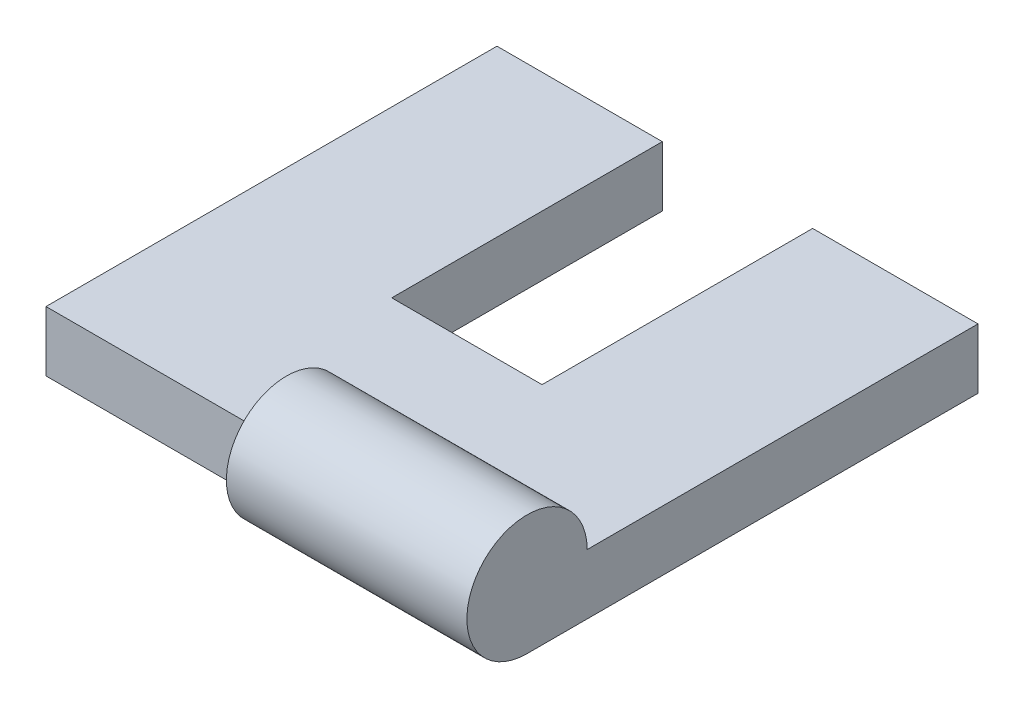
SolidWorks part; units mm, degrees
ref_plane "Front Plane" through (0, 0, 0) normal (0, 0, 1) x (1, 0, 0)
ref_plane "Top Plane" through (0, 0, 0) normal (0, 1, 0) x (1, 0, 0)
ref_plane "Right Plane" through (0, 0, 0) normal (1, 0, 0) x (0, 0, -1)
sketch "Sketch1" plane through (0, 0, 0) normal (0, 1, 0) x (1, 0, 0)
  line L2 (18.0696, -158.0434) -> (2.0696, -158.0434)
  line L3 (18.0696, -158.0434) -> (18.0696, -173.0434)
  line L4 (18.0696, -173.0434) -> (2.0696, -173.0434)
  line L5 (2.0696, -158.0434) -> (2.0696, -173.0434)
  dimension "D1" = 15
  dimension "D2" = 16
extrude "Boss-Extrude1" add sketch "Sketch1" along normal blind 2
sketch "Sketch2" plane through (18.0696, 0, 0) normal (1, 0, 0) x (0, 0, -1)
  circle A0 centre (-173.0434, 2) radius 2
extrude "Boss-Extrude2" add sketch "Sketch2" against normal blind 8
sketch "Sketch3" plane through (0, 0, 0) normal (0, -1, 0) x (-1, 0, 0)
  line L0 (-18.0696, -158.0434) -> (-2.0696, -158.0434) construction
  line L1 (-7.5696, -158.0434) -> (-12.5696, -158.0434)
  line L2 (-7.5696, -158.0434) -> (-7.5696, -167.0434)
  line L3 (-7.5696, -167.0434) -> (-12.5696, -167.0434)
  line L4 (-12.5696, -158.0434) -> (-12.5696, -167.0434)
  point P4 (-10.0696, -158.0434)
  point P7 (-10.0696, -158.0434)
  dimension "D1" = 5
  dimension "D2" = 9
extrude "Cut-Extrude1" cut sketch "Sketch3" against normal blind 10
